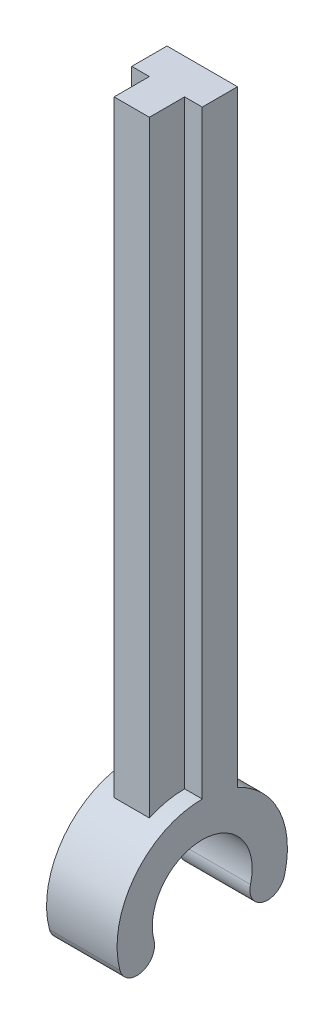
SolidWorks part; units mm, degrees
ref_plane "Front" through (0, 0, 0) normal (0, 0, 1) x (1, 0, 0)
ref_plane "Top" through (0, 0, 0) normal (0, 1, 0) x (1, 0, 0)
ref_plane "Right" through (0, 0, 0) normal (1, 0, 0) x (0, 0, -1)
sketch "Sketch1" plane through (0, 0, 0) normal (1, 0, 0) x (0, 0, -1)
  line L0 (0, 0) -> (-7.25, 0)
  line L1 (0, 0) -> (-7.003, -1.8764)
  line L2 (0, 50) -> (0, -50) construction
  line L3 (0, 0) -> (7.003, -1.8764)
  line L4 (-7.003, -1.8764) -> (-5.5541, -1.4882)
  circle A0 centre (0, 0) radius 4.25
  circle A1 centre (0, 0) radius 7.25
  arc A2 (-7.003, -1.8764) -> (-4.1052, -1.1) centre (-5.5541, -1.4882) ccw
  arc A3 (7.003, -1.8764) -> (4.1052, -1.1) centre (5.5541, -1.4882) cw
  dimension "D1" = 15
  dimension "D3" = 14.5
  dimension "D4" = 8.5
  dimension "D2" = 1.5
extrude "Boss-Extrude1" add sketch "Sketch1" against normal blind 3 and the other way blind 3 contours L3 A1 L0 A0 | A3 L3 | L0 A1 L1 A0 | L1 A2 region at (0, -0.7654, 5.8135) region at (0, 0.1713, 5.75) region at (0, -2.1031, 5.3893) region at (0, -2.1031, -5.3893)
sketch "Sketch2" plane through (0, 0, 0) normal (1, 0, 0) x (0, 0, -1)
  line L0 (0, 0) -> (0, 7.25)
  line L1 (0, 7.25) -> (0, 5.25)
  line L2 (0, 5.25) -> (-3, 5.25)
  line L3 (0, 58.25) -> (0, 5.25)
  line L4 (-3, 5.25) -> (3, 5.25)
  line L5 (-3, 5.25) -> (-3, 58.25)
  line L6 (-3, 58.25) -> (3, 58.25)
  line L7 (3, 5.25) -> (3, 58.25)
  arc A0 (7.003, -1.8764) -> (-7.003, -1.8764) centre (0, 0) ccw construction
  dimension "D1" = 2
  dimension "D2" = 3
  dimension "D3" = 6
  dimension "D4" = 53
extrude "Boss-Extrude2" add sketch "Sketch2" along normal blind 3 and the other way blind 3 contours L4 L7 L6 L3 L0 region at (0, 31.75, -1.5)
sketch "Sketch3" plane through (0, 0, 0) normal (1, 0, 0) x (0, 0, -1)
  line L1 (0, 58.25) -> (-3, 58.25)
  line L2 (0, 58.25) -> (0, 6.25)
  line L3 (0, 6.25) -> (-3, 6.25)
  line L4 (-3, 58.25) -> (-3, 6.25)
  dimension "D1" = 52
  dimension "D2" = 3
extrude "Boss-Extrude3" add sketch "Sketch3" along normal blind 1.5 and the other way blind 1.5
